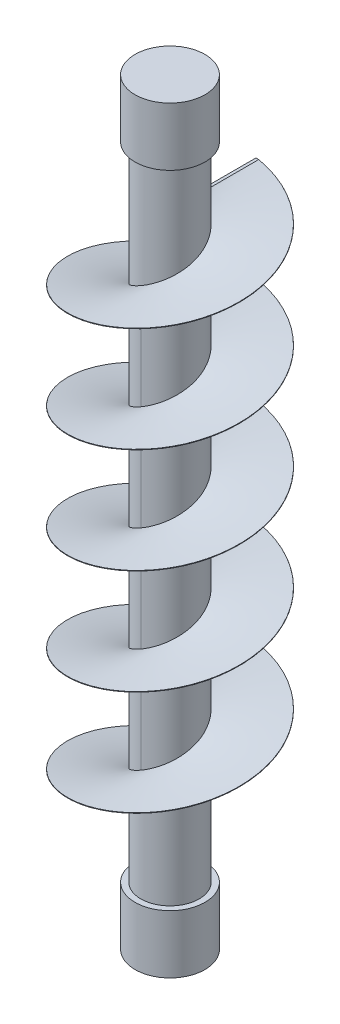
SolidWorks part; units mm, degrees
ref_plane "Front Plane" through (0, 0, 0) normal (0, 0, 1) x (1, 0, 0)
ref_plane "Top Plane" through (0, 0, 0) normal (0, 1, 0) x (1, 0, 0)
ref_plane "Right Plane" through (0, 0, 0) normal (1, 0, 0) x (0, 0, -1)
sketch "Sketch1" plane through (0, 0, 0) normal (0, 1, 0) x (1, 0, 0)
  circle A0 centre (0, 0) radius 25
  dimension "D1" = 50
extrude "Boss-Extrude1" add sketch "Sketch1" against normal blind 500
sketch "Sketch2" plane through (0, 0, 0) normal (0, 1, 0) x (1, 0, 0)
  circle A0 centre (0, 0) radius 75
  dimension "D1" = 150
curve "Helix/Spiral1" pitch 90 height 450 radius 75 centre (0, 0, 0) axis (0, -1, 0) start towards (0, 0, 1)
sketch "Sketch3" plane through (0, 0, 0) normal (0, 1, 0) x (1, 0, 0)
  line L0 (0, 74.9099) -> (0, 76.5829) construction
  line L1 (-1.2, 74.9003) -> (-1.2, 24.9712)
  line L2 (1.2, 74.9003) -> (1.2, 24.9712)
  arc A1 (-1.2, 74.9003) -> (1.2, 74.9003) centre (0, 0) cw
  arc A3 (-1.2, 24.9712) -> (1.2, 24.9712) centre (0, 0) cw
  dimension "D1" = 1.2
  dimension "D2" = 1.2
sweep "Sweep1" add profiles "Sketch3" path "Helix/Spiral1"
sketch "Sketch5" plane through (0, 0, 0) normal (0, 1, 0) x (1, 0, 0)
  circle A0 centre (0, 0) radius 25
extrude "Boss-Extrude2" add sketch "Sketch5" along normal blind 50
sketch "Sketch6" plane through (0, 50, 0) normal (0, 1, 0) x (1, 0, 0)
  circle A0 centre (0, 0) radius 30
  dimension "D1" = 60
extrude "Boss-Extrude3" add sketch "Sketch6" along normal blind 50
sketch "Sketch7" plane through (0, -500, 0) normal (0, -1, 0) x (1, 0, 0)
  circle A0 centre (0, 0) radius 30
  dimension "D1" = 60
extrude "Boss-Extrude4" add sketch "Sketch7" along normal blind 50
